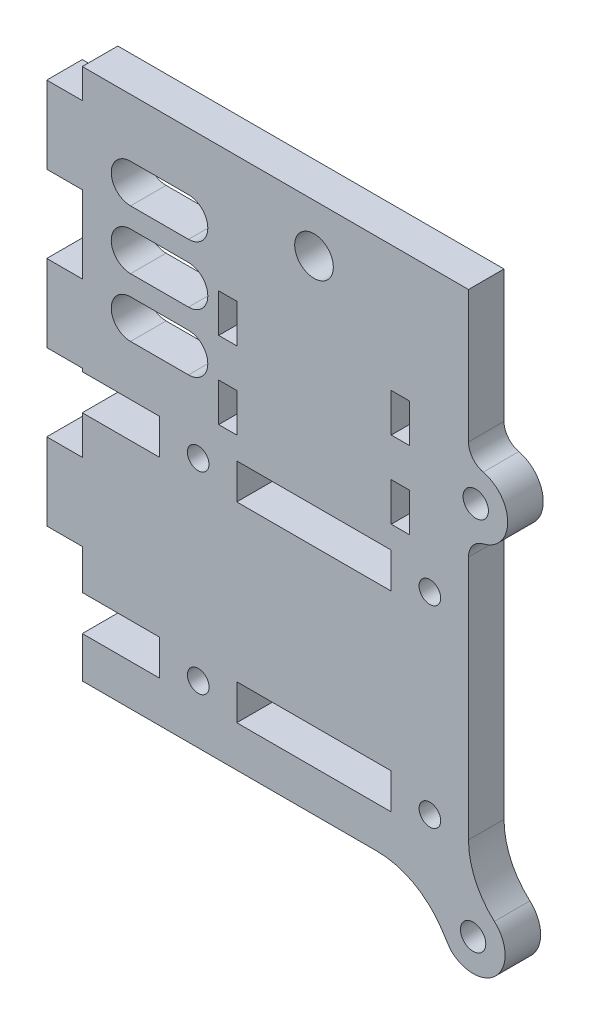
SolidWorks part; units mm, degrees
ref_plane "Front Plane" through (0, 0, 0) normal (0, 0, 1) x (1, 0, 0)
ref_plane "Top Plane" through (0, 0, 0) normal (0, 1, 0) x (1, 0, 0)
ref_plane "Right Plane" through (0, 0, 0) normal (1, 0, 0) x (0, 0, -1)
sketch "Sketch1" plane through (0, 0, 0) normal (0, 0, 1) x (1, 0, 0)
  line L0 (0, 0) -> (0, -12.7) construction
  line L1 (-5.842, 12.7) -> (0, 12.7)
  line L3 (-5.842, 0) -> (0, 0)
  line L4 (0, 0) -> (0, -12.7)
  line L5 (-53.8955, 12.7) -> (-53.8955, -55.5432) construction
  line L6 (0, -50.8) -> (0, -57.3499)
  line L7 (-5.842, -12.7) -> (0, -12.7)
  line L9 (0, -25.908) -> (63.5, -25.908) construction
  line L10 (0, 0) -> (0, -12.7)
  line L11 (0, -31.75) -> (0, -38.1) construction
  line L12 (12.7, -28.702) -> (25.4, -28.702) construction
  line L13 (-5.842, -38.1) -> (0, -38.1)
  line L15 (-5.842, -50.8) -> (0, -50.8)
  line L16 (12.716, -60.3979) -> (25.416, -60.3979) construction
  line L17 (0, -31.75) -> (0, -38.1)
  line L18 (0, -25.908) -> (12.7, -25.908)
  line L19 (50.8, -63.1919) -> (63.5, -63.1919)
  line L20 (0, -31.75) -> (12.7, -31.75)
  line L21 (12.7, -25.908) -> (12.7, -31.75)
  line L22 (0, 17.5501) -> (63.5, 17.5501)
  line L23 (0, 17.5501) -> (0, 12.7)
  line L24 (12.7, -63.1919) -> (25.4, -63.1919)
  line L25 (63.5, 17.5501) -> (63.5, -63.1919)
  line L26 (0, -57.3499) -> (12.7, -57.3499)
  line L27 (25.4, -25.908) -> (50.8, -25.908)
  line L28 (25.4, -25.908) -> (25.4, -31.75)
  line L29 (12.7, -57.3499) -> (12.7, -63.1919)
  line L30 (25.4, -31.75) -> (50.8, -31.75)
  line L31 (50.8, -25.908) -> (50.8, -31.75)
  line L32 (25.4, -57.3499) -> (50.8, -57.3499)
  line L33 (25.4, -57.3499) -> (25.4, -63.1919)
  line L34 (-5.842, -25.4) -> (0, -25.4)
  line L35 (50.8, -57.3499) -> (50.8, -63.1919)
  line L36 (0, -25.4) -> (0, -25.908)
  line L37 (50.8, -28.702) -> (63.5, -28.702) construction
  line L38 (50.816, -60.3979) -> (63.5, -60.3979) construction
  line L40 (22.114, -63.4459) -> (16.018, -63.4459) construction
  line L41 (22.114, -63.4459) -> (22.114, -57.3499) construction
  line L42 (22.114, -57.3499) -> (16.018, -57.3499) construction
  line L43 (16.018, -63.4459) -> (16.018, -57.3499) construction
  line L44 (22.114, -63.4459) -> (16.018, -57.3499) construction
  line L45 (22.114, -57.3499) -> (16.018, -63.4459) construction
  line L46 (22.098, -25.654) -> (16.002, -25.654) construction
  line L47 (22.098, -25.654) -> (22.098, -31.75) construction
  line L48 (22.098, -31.75) -> (16.002, -31.75) construction
  line L49 (16.002, -25.654) -> (16.002, -31.75) construction
  line L50 (22.098, -25.654) -> (16.002, -31.75) construction
  line L51 (22.098, -31.75) -> (16.002, -25.654) construction
  line L55 (-5.842, 12.7) -> (-5.842, -50.8)
  circle A0 centre (19.05, -28.702) radius 1.778
  circle A1 centre (19.066, -60.3979) radius 1.778
  circle A2 centre (57.15, -28.702) radius 1.778
  circle A3 centre (57.158, -60.3979) radius 1.778
  dimension "D20" = 3.556
  dimension "D21" = 3.556
  dimension "D23" = 3.556
  dimension "D24" = 3.556
  dimension "D2" = 53.8955
  dimension "D3" = 0.508
  dimension "D4" = 5.842
  dimension "D5" = 12.7
  dimension "D6" = 4.8501
  dimension "D7" = 6.5499
  dimension "D8" = 12.7
  dimension "D9" = 5.842
  dimension "D10" = 5.842
  dimension "D11" = 25.4
  dimension "D12" = 12.7
  dimension "D13" = 5.842
  dimension "D14" = 25.4
  dimension "D15" = 12.7
  dimension "D16" = 12.7
  dimension "D18" = 6.35
  dimension "D19" = 12.7
  dimension "D22" = 63.5
  dimension "D25" = 6.096
  dimension "D26" = 6.096
  dimension "D27" = 3.048
  dimension "D28" = 6.096
  dimension "D29" = 6.096
  dimension "D30" = 5.842
extrude "Boss-Extrude1" add sketch "Sketch1" along normal blind 5.842 contours L32 L35 L19 L25 L22 L23 L1 L3 L4 L7 L18 L21 L20 L17 L13 L15 L6 L26 L29 L24 L33 L31 region at (30.4992, -20.4826, 0)
sketch "Sketch2" plane through (0, 0, 5.842) normal (0, 0, 1) x (1, 0, 0)
  line L0 (63.5, -63.1919) -> (0, -63.1919)
  line L1 (63.5, -69.9498) -> (0, -69.9498)
  line L2 (0, -69.9498) -> (0, -63.1919)
  line L3 (63.5, -69.9498) -> (63.5, -63.1919)
  dimension "D1" = 6.7579
extrude "Boss-Extrude2" add sketch "Sketch2" against normal up to surface (5.842 mm away) up to face at (58.936, -60.3979, 0)
fillet "Fillet1" radius 3.175 1 edges at (63.5, -69.9498, 2.921)
sketch "Sketch3" plane through (0, 0, 5.842) normal (0, 0, 1) x (1, 0, 0)
  line L0 (38.1, -31.75) -> (38.1, -57.3499) construction
  line L1 (25.4, -31.75) -> (50.8, -31.75) construction
  line L2 (25.4, -57.3499) -> (50.8, -57.3499) construction
  line L3 (38.1, -44.5499) -> (-5.842, -44.45) construction
  line L4 (-5.842, -38.1) -> (-5.842, -50.8) construction
  line L5 (49.2125, -38.1855) -> (39.6875, -50.8855) construction
  line L6 (26.9875, -50.8855) -> (36.5125, -50.8855)
  line L7 (26.9875, -50.8855) -> (26.9875, -38.1855)
  line L8 (26.9875, -38.1855) -> (36.5125, -38.1855)
  line L9 (36.5125, -50.8855) -> (36.5125, -38.1855)
  line L10 (26.9875, -50.8855) -> (36.5125, -38.1855) construction
  line L11 (26.9875, -38.1855) -> (36.5125, -50.8855) construction
  line L12 (49.2125, -50.8855) -> (39.6875, -38.1855) construction
  line L13 (39.6875, -50.8855) -> (39.6875, -38.1855)
  line L14 (49.2125, -38.1855) -> (39.6875, -38.1855)
  line L15 (49.2125, -50.8855) -> (49.2125, -38.1855)
  line L16 (49.2125, -50.8855) -> (39.6875, -50.8855)
  point P10 (31.75, -44.5355)
  point P19 (44.45, -44.5355)
  dimension "D1" = 9.525
  dimension "D2" = 12.7
  dimension "D3" = 6.35
extrude "Cut-Extrude1" [suppressed] cut sketch "Sketch3" against normal through all
fillet "Fillet2" [suppressed] radius 3.175
sketch "Sketch4" plane through (0, 0, 5.842) normal (0, 0, 1) x (1, 0, 0)
  line L0 (38.1, -25.908) -> (38.1, 17.5501) construction
  line L1 (25.4, -25.908) -> (50.8, -25.908) construction
  line L2 (0, 17.5501) -> (63.5, 17.5501) construction
  line L3 (0, -12.7) -> (63.5, -12.7) construction
  line L4 (50.8, -25.3124) -> (25.4, -25.3124) construction
  line L5 (50.8, -25.3124) -> (50.8, 0.0876) construction
  line L6 (50.8, 0.0876) -> (25.4, 0.0876) construction
  line L7 (25.4, -25.3124) -> (25.4, 0.0876) construction
  line L8 (50.8, -25.3124) -> (25.4, 0.0876) construction
  line L9 (50.8, 0.0876) -> (25.4, -25.3124) construction
  line L10 (63.5, 17.5501) -> (63.5, -66.7748) construction
  line L11 (22.425, -15.875) -> (25.4, -22.225) construction
  line L12 (22.425, -3.175) -> (25.4, -3.175)
  line L13 (22.425, -3.175) -> (22.425, -9.525)
  line L14 (22.425, -9.525) -> (25.4, -9.525)
  line L15 (25.4, -3.175) -> (25.4, -9.525)
  line L16 (22.425, -3.175) -> (25.4, -9.525) construction
  line L17 (22.425, -9.525) -> (25.4, -3.175) construction
  line L18 (22.425, -22.225) -> (25.4, -15.875) construction
  line L19 (25.4, -22.225) -> (25.4, -15.875)
  line L20 (22.425, -15.875) -> (25.4, -15.875)
  line L21 (22.425, -22.225) -> (22.425, -15.875)
  line L22 (22.425, -22.225) -> (25.4, -22.225)
  line L23 (53.775, -22.225) -> (50.8, -15.875) construction
  line L24 (53.775, -9.525) -> (50.8, -3.175) construction
  line L25 (53.775, -3.175) -> (50.8, -9.525) construction
  line L26 (53.775, -15.875) -> (50.8, -22.225) construction
  line L27 (53.775, -22.225) -> (50.8, -22.225)
  line L28 (53.775, -22.225) -> (53.775, -15.875)
  line L29 (53.775, -15.875) -> (50.8, -15.875)
  line L30 (50.8, -22.225) -> (50.8, -15.875)
  line L31 (50.8, -3.175) -> (50.8, -9.525)
  line L32 (53.775, -9.525) -> (50.8, -9.525)
  line L33 (53.775, -3.175) -> (53.775, -9.525)
  line L34 (53.775, -3.175) -> (50.8, -3.175)
  circle A0 centre (38.1, 9.6126) radius 3.175
  point P8 (38.1, -12.6124)
  point P18 (23.9125, -6.35)
  point P27 (23.9125, -19.05)
  point P36 (52.2875, -19.05)
  point P37 (52.2875, -6.35)
  dimension "D1" = 6.35
  dimension "D2" = 7.9375
  dimension "D3" = 25.4
  dimension "D4" = 25.4
  dimension "D5" = 9.525
  dimension "D6" = 2.975
  dimension "D7" = 6.35
  dimension "D8" = 3.175
extrude "Cut-Extrude2" cut sketch "Sketch4" against normal through all
sketch "Sketch5" plane through (0, 0, 5.842) normal (0, 0, 1) x (1, 0, 0)
  line L0 (0, 17.5501) -> (63.5, 17.5501) construction
  line L2 (0, -6.35) -> (22.225, -6.35) construction
  line L3 (0, 0) -> (0, -12.7) construction
  line L4 (7.9375, -4.8019) -> (17.4625, -4.8019) construction
  line L6 (7.9375, 4.8501) -> (17.4625, 4.8501) construction
  line L7 (7.9375, 8.0251) -> (17.4625, 8.0251)
  line L8 (7.9375, 1.6751) -> (17.4625, 1.6751)
  line L9 (7.9375, -1.6269) -> (17.4625, -1.6269)
  line L10 (7.9375, -7.9769) -> (17.4625, -7.9769)
  line L11 (7.9375, -14.4539) -> (17.4625, -14.4539) construction
  line L12 (7.9375, -11.2789) -> (17.4625, -11.2789)
  line L13 (7.9375, -17.6289) -> (17.4625, -17.6289)
  arc A1 (7.9375, 8.0251) -> (7.9375, 1.6751) centre (7.9375, 4.8501) ccw
  arc A2 (17.4625, 1.6751) -> (17.4625, 8.0251) centre (17.4625, 4.8501) ccw
  arc A3 (7.9375, -1.6269) -> (7.9375, -7.9769) centre (7.9375, -4.8019) ccw
  arc A4 (17.4625, -7.9769) -> (17.4625, -1.6269) centre (17.4625, -4.8019) ccw
  arc A5 (7.9375, -11.2789) -> (7.9375, -17.6289) centre (7.9375, -14.4539) ccw
  arc A6 (17.4625, -17.6289) -> (17.4625, -11.2789) centre (17.4625, -14.4539) ccw
  point P5 (12.7, -4.8019)
  point P17 (12.7, 4.8501)
  point P24 (12.7, -14.4539)
  dimension "D2" = 3.175
  dimension "D1" = 9.525
  dimension "D3" = 12.7
  dimension "D5" = 3
  dimension "D4" = 9.525
sketch "Sketch6" plane through (0, 0, 5.842) normal (0, 0, 1) x (1, 0, 0)
  line L0 (63.5, -7.8499) -> (139.7, 17.5501)
  line L1 (63.5, 17.5501) -> (63.5, -66.7748) construction
  line L2 (63.5, -7.8499) -> (63.5, 17.5501)
  line L3 (139.7, 17.5501) -> (63.5, 17.5501)
  line L4 (69.85, 0.9603) -> (100.5695, 11.2001)
  line L5 (100.5695, 11.2001) -> (69.85, 11.2001)
  line L6 (69.85, 0.9603) -> (69.85, 11.2001)
  dimension "D1" = 25.4
  dimension "D2" = 76.2
  dimension "D3" = 6.35
extrude "Boss-Extrude3" [suppressed] add sketch "Sketch6" against normal up to surface (5.842 mm away)
fillet "Fillet9" [suppressed] radius 12.7
fillet "Fillet10" [suppressed] radius 0.7937
fillet "Fillet11" [suppressed] radius 1.5875
extrude "Cut-Extrude3" cut sketch "Sketch5" against normal through all
sketch "Sketch7" plane through (0, 0, 5.842) normal (0, 0, 1) x (1, 0, 0)
  line L0 (63.5, 17.5501) -> (63.5, -66.7748) construction
  line L1 (64.262, -74.2322) -> (60.0456, -74.2322) construction
  line L2 (64.262, -74.2322) -> (60.5442, -77.95) construction
  line L3 (60.5442, -77.95) -> (55.2185, -69.9498)
  line L4 (0, -69.9498) -> (60.325, -69.9498) construction
  line L5 (55.2185, -69.9498) -> (60.325, -69.9498)
  line L6 (63.5, -66.7748) -> (67.6153, -70.1825)
  circle A0 centre (64.262, -74.2322) radius 2.0828
  arc A1 (60.5442, -77.95) -> (67.6153, -70.1825) centre (64.262, -74.2322) ccw
  arc A2 (60.325, -69.9498) -> (63.5, -66.7748) centre (60.325, -66.7748) ccw construction
  arc A3 (60.325, -69.9498) -> (63.5, -66.7748) centre (60.325, -66.7748) ccw
  circle A5 centre (64.262, -74.2322) radius 5.2578 construction
  point P7 (68.2942, -71.7977)
  dimension "D1" = 4.1656
  dimension "D2" = 0.762
  dimension "D4" = 45
  dimension "D3" = 3.175
extrude "Boss-Extrude4" add sketch "Sketch7" against normal up to surface (5.842 mm away) up to face at (12.7, -14.4539, 0)
fillet "Fillet12" radius 12.7 2 edges at (55.2185, -69.9498, 2.921) (63.5, -66.7748, 2.921)
sketch "Sketch8" plane through (0, 0, 5.842) normal (0, 0, 1) x (1, 0, 0)
  line L0 (63.5, 17.5501) -> (63.5, -60.817) construction
  line L1 (0, -69.9498) -> (48.4162, -69.9498) construction
  line L2 (64.6935, -17.6103) -> (63.5, -17.6103)
  line L3 (63.5, -17.6103) -> (63.5, -17.4731)
  line L4 (64.6935, -7.0947) -> (63.5, -7.0947)
  line L5 (63.5, -7.0947) -> (63.5, -7.232)
  circle A0 centre (64.6935, -12.3525) radius 2.0828
  arc A1 (64.6935, -17.6103) -> (64.6935, -7.0947) centre (64.6935, -12.3525) ccw
  arc A2 (63.5, -7.232) -> (63.5, -17.4731) centre (64.6935, -12.3525) ccw
  circle A3 centre (64.6935, -12.3525) radius 5.2578 construction
  point P10 (69.9513, -12.3525)
  dimension "D1" = 4.1656
  dimension "D2" = 1.1935
  dimension "D3" = 57.5973
  dimension "D4" = 3.175
extrude "Boss-Extrude5" add sketch "Sketch8" against normal up to surface (5.842 mm away) up to face at (13.6459, -34.9045, 0)
fillet "Fillet13" radius 3.175 2 edges at (63.5, -17.6103, 2.921) (63.5, -7.0947, 2.921)
sketch "Sketch9" plane through (0, 0, 5.842) normal (0, 0, 1) x (1, 0, 0)
  circle A0 centre (64.6935, -12.3525) radius 2.0828
extrude "Cut-Extrude4" cut sketch "Sketch9" against normal through all
sketch "Sketch10" [suppressed] plane through (0, 0, 5.842) normal (0, 0, 1) x (1, 0, 0)
  line L0 (0, -88.2063) -> (0, -146.1498)
  line L1 (38.1, -69.9498) -> (3.175, -171.5498)
  line L2 (0, -69.9498) -> (48.4162, -69.9498) construction
  line L3 (3.175, -171.5498) -> (0, -171.5498)
  line L4 (38.1, -69.9498) -> (0, -69.9498)
  line L5 (9.525, -79.4748) -> (9.525, -123.7766)
  line L6 (9.525, -123.7766) -> (9.525, -123.7766)
  line L7 (24.7537, -79.4748) -> (9.525, -123.7766)
  line L8 (24.7537, -79.4748) -> (9.525, -79.4748)
  line L9 (0, -69.6643) -> (-5.842, -69.6643)
  line L10 (0, -63.1919) -> (0, -69.9498) construction
  line L11 (-5.842, -69.6643) -> (-5.842, -82.3643)
  line L12 (0, -69.9498) -> (0, -69.6643)
  line L13 (0, -69.9498) -> (0, -171.5498) construction
  line L14 (-5.842, -82.3643) -> (0, -88.2063)
  line L15 (0, -171.5498) -> (-9.525, -171.5498)
  line L16 (-9.525, -171.5498) -> (-9.525, -158.8498)
  line L17 (-9.525, -158.8498) -> (0, -146.1498)
  line L18 (-9.525, -165.1998) -> (5.3578, -165.1998) construction
  circle A0 centre (9.525, -130.1266) radius 2.0828
  circle A1 centre (-2.0836, -165.1998) radius 2.0828
  dimension "D5" = 4.1656
  dimension "D13" = 4.1656
  dimension "D1" = 101.6
  dimension "D2" = 3.175
  dimension "D3" = 38.1
  dimension "D6" = 6.35
  dimension "D7" = 5.842
  dimension "D8" = 0.2855
  dimension "D9" = 12.7
  dimension "D10" = 12.7
  dimension "D11" = 9.525
  dimension "D12" = 25.4
  dimension "D4" = 9.525
extrude "Boss-Extrude6" [suppressed] add sketch "Sketch10" against normal up to surface (5.842 mm away)
fillet "Fillet14" [suppressed] radius 2.54
fillet "Fillet15" [suppressed] radius 6.35
fillet "Fillet16" [suppressed] radius 6.35
sketch "Sketch11" [suppressed] plane through (0, 0, 5.842) normal (0, 0, 1) x (1, 0, 0)
  line L0 (38.1, -25.908) -> (38.1, 17.5501) construction
  line L1 (25.4, -25.908) -> (50.8, -25.908) construction
  line L2 (0, 17.5501) -> (63.5, 17.5501) construction
  circle A0 centre (38.1, -4.1789) radius 9.525
extrude "Cut-Extrude5" [suppressed] cut sketch "Sketch11" against normal through all
